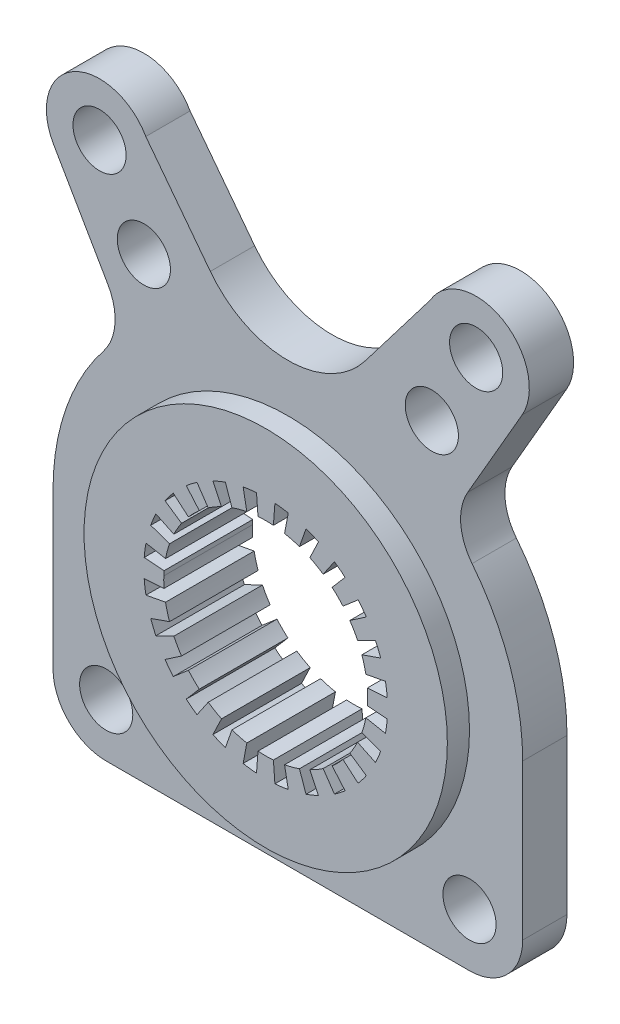
SolidWorks part; units mm, degrees
ref_plane "Front Plane" through (0, 0, 0) normal (0, 0, 1) x (1, 0, 0)
ref_plane "Top Plane" through (0, 0, 0) normal (0, 1, 0) x (1, 0, 0)
ref_plane "Right Plane" through (0, 0, 0) normal (1, 0, 0) x (0, 0, -1)
sketch "Sketch2" plane through (0, 0, 0) normal (0, 0, 1) x (1, 0, 0)
  line L0 (-60.7832, 0) -> (59.2993, 0) construction
  line L1 (0, 83.037) -> (0, -87.4309) construction
  line L2 (120.2466, 0) -> (-150.9098, 0) construction
  line L3 (-148.6376, -35) -> (126.7336, -35) construction
  line L4 (-53, 0) -> (-53, -35)
  line L5 (53, 0) -> (53, -35)
  line L6 (-41, -18.8222) -> (-41, -80.6403) construction
  line L7 (41, -12.719) -> (41, -78.7519) construction
  line L8 (-41, -47) -> (41, -47)
  line L9 (0, 0) -> (-67.0162, 116.0755) construction
  line L10 (0, 0) -> (61.8273, 107.088) construction
  line L11 (-42.5, 73.6122) -> (-32.5, 56.2917) construction
  line L12 (-32.061, 79.5305) -> (-17.495, 60.4553)
  line L13 (-52.8923, 67.6122) -> (-40.5958, 46.314)
  line L14 (42.5, 73.6122) -> (32.5, 56.2917) construction
  line L15 (52.8923, 67.6122) -> (40.5958, 46.314)
  line L16 (32.1205, 79.6343) -> (17.4753, 60.4553)
  line L17 (-27.4215, -2.0763) -> (-22.9344, -1.7365)
  line L22 (-27.4215, 2.0767) -> (-22.9343, 1.7369)
  line L23 (-27.0245, 5.0917) -> (-22.6023, 4.2585)
  line L24 (-25.9496, 9.1031) -> (-21.7033, 7.6135)
  line L25 (-24.7859, 11.9126) -> (-20.73, 9.9633)
  line L26 (-22.7094, 15.5092) -> (-18.9933, 12.9713)
  line L27 (-20.8581, 17.9218) -> (-17.4449, 14.9891)
  line L28 (-17.9215, 20.8583) -> (-14.9889, 17.4452)
  line L29 (-15.5089, 22.7096) -> (-12.971, 18.9935)
  line L30 (-11.9123, 24.786) -> (-9.963, 20.7301)
  line L31 (-9.1027, 25.9498) -> (-7.6132, 21.7034)
  line L32 (-5.0913, 27.0246) -> (-4.2582, 22.6024)
  line L33 (-2.0763, 27.4215) -> (-1.7365, 22.9344)
  line L34 (2.0767, 27.4215) -> (1.7369, 22.9343)
  line L35 (5.0917, 27.0245) -> (4.2585, 22.6023)
  line L36 (9.1031, 25.9496) -> (7.6135, 21.7033)
  line L37 (11.9126, 24.7859) -> (9.9633, 20.73)
  line L38 (15.5092, 22.7094) -> (12.9713, 18.9933)
  line L39 (17.9218, 20.8581) -> (14.9891, 17.4449)
  line L40 (20.8583, 17.9215) -> (17.4452, 14.9889)
  line L41 (22.7096, 15.5089) -> (18.9935, 12.971)
  line L42 (24.786, 11.9123) -> (20.7301, 9.963)
  line L43 (25.9498, 9.1027) -> (21.7034, 7.6132)
  line L44 (27.0246, 5.0913) -> (22.6024, 4.2582)
  line L45 (27.4215, 2.0763) -> (22.9344, 1.7365)
  line L46 (27.4215, -2.0767) -> (22.9343, -1.7369)
  line L47 (27.0245, -5.0917) -> (22.6023, -4.2585)
  line L48 (25.9496, -9.1031) -> (21.7033, -7.6135)
  line L49 (24.7859, -11.9126) -> (20.73, -9.9633)
  line L50 (22.7094, -15.5092) -> (18.9933, -12.9713)
  line L51 (20.8581, -17.9218) -> (17.4449, -14.9891)
  line L52 (17.9215, -20.8583) -> (14.9889, -17.4452)
  line L53 (15.5089, -22.7096) -> (12.971, -18.9935)
  line L54 (11.9123, -24.786) -> (9.963, -20.7301)
  line L55 (9.1027, -25.9498) -> (7.6132, -21.7034)
  line L56 (5.0913, -27.0246) -> (4.2582, -22.6024)
  line L57 (2.0763, -27.4215) -> (1.7365, -22.9344)
  line L58 (-2.0767, -27.4215) -> (-1.7369, -22.9343)
  line L59 (-5.0917, -27.0245) -> (-4.2585, -22.6023)
  line L60 (-9.1031, -25.9496) -> (-7.6135, -21.7033)
  line L61 (-11.9126, -24.7859) -> (-9.9633, -20.73)
  line L62 (-15.5092, -22.7094) -> (-12.9713, -18.9933)
  line L63 (-17.9218, -20.8581) -> (-14.9891, -17.4449)
  line L64 (-20.8583, -17.9215) -> (-17.4452, -14.9889)
  line L65 (-22.7096, -15.5089) -> (-18.9935, -12.971)
  line L66 (-24.786, -11.9123) -> (-20.7301, -9.963)
  line L67 (-25.9498, -9.1027) -> (-21.7034, -7.6132)
  line L68 (-27.0246, -5.0913) -> (-22.6024, -4.2582)
  circle A0 centre (0, 0) radius 41
  circle A1 centre (0, 0) radius 23
  circle A2 centre (0, 0) radius 27.5
  circle A3 centre (-41, -35) radius 6
  circle A4 centre (41, -35) radius 6
  arc A5 (-53, -35) -> (-41, -47) centre (-41, -35) ccw
  arc A6 (53, -35) -> (41, -47) centre (41, -35) cw
  arc A7 (-40.5958, 46.314) -> (-41.5749, 32.8714) centre (-50.9881, 40.314) cw
  arc A8 (40.5958, 46.314) -> (41.5749, 32.8714) centre (50.9881, 40.314) ccw
  circle A9 centre (32.5, 56.2917) radius 6
  circle A10 centre (42.5, 73.6122) radius 6
  circle A11 centre (-42.5, 73.6122) radius 6
  circle A12 centre (-32.5, 56.2917) radius 6
  arc A13 (-32.061, 79.5305) -> (-52.8923, 67.6122) centre (-42.5, 73.6122) ccw
  arc A15 (52.8923, 67.6122) -> (32.1205, 79.6343) centre (42.5, 73.6122) ccw
  arc A17 (-53, 0) -> (-41.5749, 32.8714) centre (0, 0) cw
  arc A18 (41.5749, 32.8714) -> (53, 0) centre (0, 0) cw
  arc A19 (-17.495, 60.4553) -> (17.4753, 60.4553) centre (-0.0099, 73.807) ccw
  arc A20 (-22.7523, 2.6768) -> (-22.9344, -1.7365) centre (-7.3864, -0.1674) ccw
  arc A21 (-27.4215, 2.0767) -> (-27.4215, -2.0763) centre (0, 0) ccw
  arc A22 (-22.7523, 2.6768) -> (-22.9344, -1.7365) centre (-7.3864, -0.1674) ccw
  circle A23 centre (0, 0) radius 23
  circle A24 centre (0, 0) radius 27.5
  circle A25 centre (0, 0) radius 23
  circle A26 centre (0, 0) radius 27.5
  circle A27 centre (0, 0) radius 23
  circle A28 centre (0, 0) radius 27.5
  circle A29 centre (0, 0) radius 23
  circle A30 centre (0, 0) radius 27.5
  circle A31 centre (0, 0) radius 23
  circle A32 centre (0, 0) radius 27.5
  circle A33 centre (0, 0) radius 23
  circle A34 centre (0, 0) radius 27.5
  circle A35 centre (0, 0) radius 23
  circle A36 centre (0, 0) radius 27.5
  circle A37 centre (0, 0) radius 23
  circle A38 centre (0, 0) radius 27.5
  circle A39 centre (0, 0) radius 23
  circle A40 centre (0, 0) radius 27.5
  circle A41 centre (0, 0) radius 23
  circle A42 centre (0, 0) radius 27.5
  circle A43 centre (0, 0) radius 23
  circle A44 centre (0, 0) radius 27.5
  circle A45 centre (0, 0) radius 23
  circle A46 centre (0, 0) radius 27.5
  circle A47 centre (0, 0) radius 23
  circle A48 centre (0, 0) radius 27.5
  circle A49 centre (0, 0) radius 23
  circle A50 centre (0, 0) radius 27.5
  circle A51 centre (0, 0) radius 23
  circle A52 centre (0, 0) radius 27.5
  circle A53 centre (0, 0) radius 23
  circle A54 centre (0, 0) radius 27.5
  circle A55 centre (0, 0) radius 23
  circle A56 centre (0, 0) radius 27.5
  circle A57 centre (0, 0) radius 23
  circle A58 centre (0, 0) radius 27.5
  circle A59 centre (0, 0) radius 23
  circle A60 centre (0, 0) radius 27.5
  circle A61 centre (0, 0) radius 23
  circle A62 centre (0, 0) radius 27.5
  circle A63 centre (0, 0) radius 23
  circle A64 centre (0, 0) radius 27.5
  circle A65 centre (0, 0) radius 23
  circle A66 centre (0, 0) radius 27.5
  circle A67 centre (0, 0) radius 23
  circle A68 centre (0, 0) radius 27.5
  point P43 (-37.5, 64.9519)
  point P48 (37.5, 64.9519)
  point P205 (0, 0)
  dimension "D1" = 82
  dimension "D2" = 46
  dimension "D3" = 55
  dimension "D4" = 35
  dimension "D8" = 12
  dimension "D10" = 12
  dimension "D9" = 12
  dimension "D11" = 12
  dimension "D13" = 12
  dimension "D14" = 12
  dimension "D17" = 12
  dimension "D18" = 12
  dimension "D19" = 12
  dimension "D20" = 12
  dimension "D23" = 12
  dimension "D24" = 12
  dimension "D25" = 53
  dimension "D26" = 53
  dimension "D27" = 22
  dimension "D5" = 35
  dimension "D6" = 82
  dimension "D7" = 41
  dimension "D12" = 12
  dimension "D15" = 30
  dimension "D16" = 30
  dimension "D21" = 65
  dimension "D22" = 20
  dimension "D28" = 4.331
  dimension "D29" = 4.33
  dimension "D30" = 24
extrude "Boss-Extrude1" add sketch "Sketch2" along normal blind 5 contours A0 A2 | L28 A2 L27 A1 | L30 A2 L29 A1 | L32 A2 L31 A1 | L34 A2 L33 A1 | L36 A2 L35 A1 | L38 A2 L37 A1 | L40 A2 L39 A1 | L42 A2 L41 A1 | L44 A2 L43 A1 | L46 A2 L45 A1 | L48 A2 L47 A1 | L50 A2 L49 A1 | L52 A2 L51 A1 | L54 A2 L53 A1 | L56 A2 L55 A1 | L58 A2 L57 A1 | L60 A2 L59 A1 | L62 A2 L61 A1 | L64 A2 L63 A1 | L66 A2 L65 A1 | L68 A2 L67 A1 | A20 A1 L22 A2 L17 | L24 A2 L23 A1 | L26 A2 L25 A1 region at (-25.296, 0.0009, 0) region at (-24.431, -6.5461, 0) region at (-24.4309, 6.5464, 0) region at (-21.9042, -12.6462, 0) region at (-21.9041, 12.6465, 0) region at (-17.8848, -17.8845, 0) region at (-17.8845, 17.8848, 0) region at (-12.6465, -21.9041, 0) region at (-12.6462, 21.9042, 0) region at (-6.5464, -24.4309, 0) region at (-6.5461, 24.431, 0) region at (-0.0002, -25.2927, 0) region at (0.0002, 25.2927, 0) region at (6.5461, -24.431, 0) region at (6.5464, 24.4309, 0) region at (12.6462, -21.9042, 0) region at (12.6465, 21.9041, 0) region at (17.8845, -17.8848, 0) region at (17.8848, 17.8845, 0) region at (21.9041, -12.6465, 0) region at (21.9042, 12.6462, 0) region at (24.4309, -6.5464, 0) region at (24.431, 6.5461, 0) region at (25.2927, -0.0002, 0) region at (-39.8403, 0, 0)
extrude "Boss-Extrude2" add sketch "Sketch2<4>" against normal blind 10 separate body contours A19 L12 A13 L13 A7 A17 L4 A5 L8 A6 L5 A18 A8 L15 A15 L16 A12 A11 A10 A9 A4 A3 A0 region at (-48.4409, 16.8366, 0)
sketch "Sketch2<4>" plane through (0, 0, 0) normal (0, 0, 1) x (1, 0, 0) same geometry as "Sketch2"
extrude "Boss-Extrude4" add sketch "Sketch2<6>" against normal blind 15 contours A0 A2 | L68 A2 L67 A1 | L66 A2 L65 A1 | L64 A2 L63 A1 | L62 A2 L61 A1 | L60 A2 L59 A1 | L58 A2 L57 A1 | L56 A2 L55 A1 | L54 A2 L53 A1 | L52 A2 L51 A1 | L50 A2 L49 A1 | L48 A2 L47 A1 | L46 A2 L45 A1 | L44 A2 L43 A1 | L42 A2 L41 A1 | L40 A2 L39 A1 | L38 A2 L37 A1 | L36 A2 L35 A1 | L34 A2 L33 A1 | L32 A2 L31 A1 | L30 A2 L29 A1 | L28 A2 L27 A1 | L26 A2 L25 A1 | L24 A2 L23 A1 | A20 A1 L22 A2 L17 region at (-25.296, 0.0009, 0) region at (-24.431, -6.5461, 0) region at (-24.4309, 6.5464, 0) region at (-21.9042, -12.6462, 0) region at (-21.9041, 12.6465, 0) region at (-17.8848, -17.8845, 0) region at (-17.8845, 17.8848, 0) region at (-12.6465, -21.9041, 0) region at (-12.6462, 21.9042, 0) region at (-6.5464, -24.4309, 0) region at (-6.5461, 24.431, 0) region at (-0.0002, -25.2927, 0) region at (0.0002, 25.2927, 0) region at (6.5461, -24.431, 0) region at (6.5464, 24.4309, 0) region at (12.6462, -21.9042, 0) region at (12.6465, 21.9041, 0) region at (17.8845, -17.8848, 0) region at (17.8848, 17.8845, 0) region at (21.9041, -12.6465, 0) region at (21.9042, 12.6462, 0) region at (24.4309, -6.5464, 0) region at (24.431, 6.5461, 0) region at (25.2927, -0.0002, 0) region at (-39.8403, 0, 0)
sketch "Sketch2<6>" plane through (0, 0, 0) normal (0, 0, 1) x (1, 0, 0) same geometry as "Sketch2"
